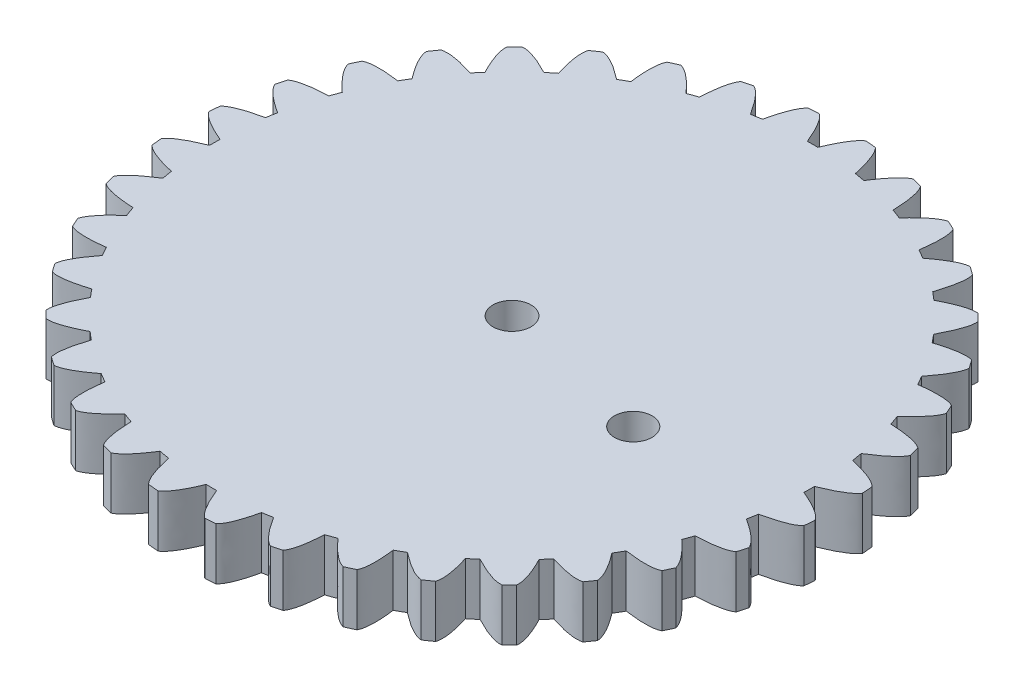
SolidWorks part; units mm, degrees
material "ABS"
ref_plane "Front Plane" through (0, 0, 0) normal (0, 0, 1) x (1, 0, 0)
ref_plane "Top Plane" through (0, 0, 0) normal (0, 1, 0) x (1, 0, 0)
ref_plane "Right Plane" through (0, 0, 0) normal (1, 0, 0) x (0, 0, -1)
sketch "Sketch1" plane through (0, 0, 0) normal (0, 1, 0) x (1, 0, 0)
  line L0 (18.9186, 21.5125) -> (21.7285, 18.6702) construction
  line L2 (20.3236, 20.0913) -> (22.457, 22.2004) construction
  line L3 (22.457, 22.2004) -> (22.5965, 22.3383)
  circle A0 centre (0, 0) radius 28.6479
  circle A1 centre (0, 0) radius 31.5781
  spline S0 degree 2 poles (21.7285, 18.6702) (24.8695, 24.5853) (18.9186, 21.5125) knots 0 0 0 1 1 1
  point P3 (18.9186, 21.5125)
  point P4 (21.7285, 18.6702)
  point P6 (22.1027, 22.5532)
  point P12 (18.1563, 22.1596)
  point P14 (22.5965, 22.3383)
  point P15 (22.8057, 21.842)
  point P16 (12.1095, 25.9627)
  dimension "D1" = 57.2958
  dimension "D4" = 3
  dimension "D5" = 1
  dimension "D2" = 4
  dimension "D3" = 1
extrude "Boss-Extrude4" add sketch "Sketch1" along normal blind 5 contours A0 | A0 S0 A1 region at (21.2325, 0, -20.9899) region at (0, 0, 0)
pattern_circular "CirPattern6" count 36 every 10 about axis through (0, 5, 0) along (0, 1, 0) of "Boss-Extrude4"
sketch "Sketch2" plane through (0, 5, 0) normal (0, 1, 0) x (1, 0, 0)
  circle A0 centre (0, 0) radius 1.825
  dimension "D1" = 3.65
extrude "Cut-Extrude2" cut sketch "Sketch2" against normal blind 10 contours A0 region at (0, 5, 0)
sketch "Sketch4" plane through (0, 0, 0) normal (0, -1, 0) x (1, 0, 0)
  circle A0 centre (15, 3.3804) radius 1.8
  circle A1 centre (0, 0) radius 1.825 construction
  dimension "D1" = 15
  dimension "D2" = 3.6
extrude "Cut-Extrude3" cut sketch "Sketch4" against normal blind 10
equation "\"number-of-teeth\" = 36"
equation "\"gear-size\"= 4mm"
equation "\"circumference\"= \"number-of-teeth\" * ( ( 1 + \"space-between-teeth\" ) * \"gear-size\" )"
equation "\"space-between-teeth\"= .25"
equation "\"D1@Sketch1\" = \"circumference\" / pi"
equation "\"D2@Sketch1\"=\"gear-size\""
equation "\"gear-length\"= 3mm"
equation "\"D4@Sketch1\"=\"gear-length\""
equation "\"D5@Sketch1\"=\"gear-size\" * \"space-between-teeth\""
equation "\"D3@Sketch1\"=\"gear-size\" * \"space-between-teeth\""
equation "\"D1@CirPattern6\"=\"number-of-teeth\""
equation "\"D2@CirPattern6\"=360 / \"number-of-teeth\""
